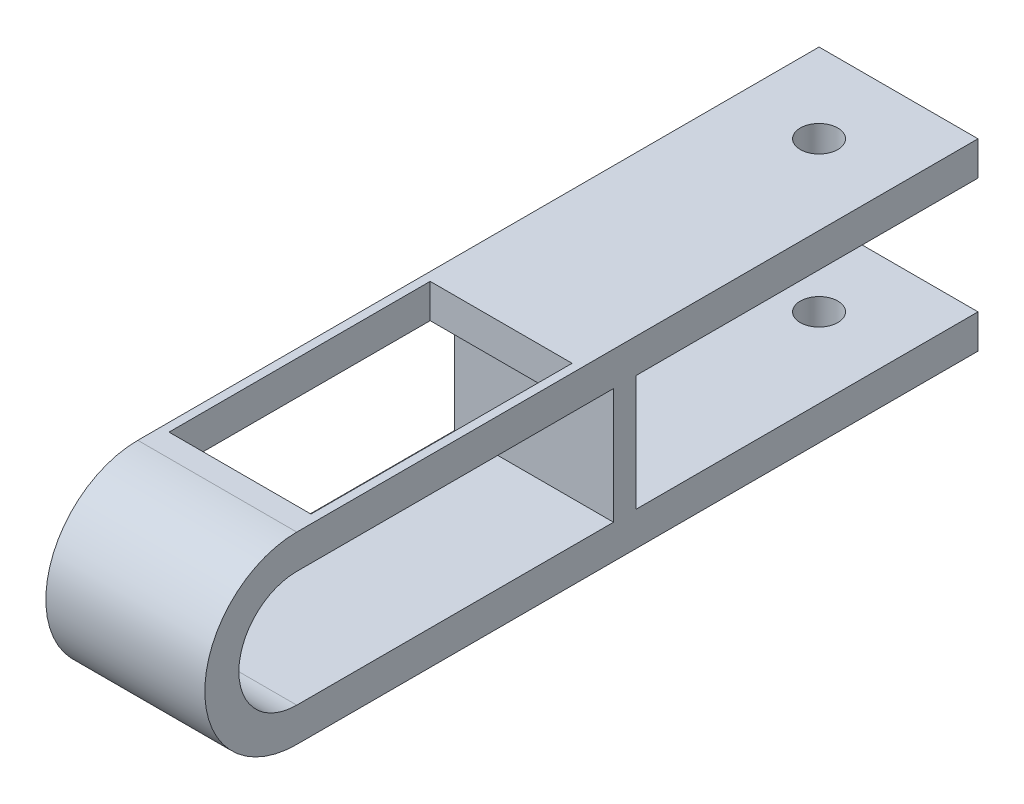
SolidWorks part; units mm, degrees
ref_plane "Front Plane" through (0, 0, 0) normal (1, 0, 0) x (0, 1, 0)
ref_plane "Top Plane" through (0, 0, 0) normal (0, 0, 1) x (0, 1, 0)
ref_plane "Right Plane" through (0, 0, 0) normal (0, 1, 0) x (-1, 0, 0)
sketch "Sketch2" plane through (0, 0, 0) normal (1, 0, 0) x (0, 1, 0)
  line L0 (0, 0) -> (0, 67.6733) construction
  line L1 (8.1, 0) -> (5.1, 0)
  line L3 (-8.1, 60) -> (-8.1, 0)
  line L4 (-8.1, 0) -> (-5.1, 0)
  line L5 (-5.1, 60) -> (-5.1, 32.1)
  line L6 (5.1, 60) -> (5.1, 32.1)
  line L8 (8.1, 60) -> (8.1, 0)
  line L9 (0, 0) -> (-21.6048, 0) construction
  line L10 (-5.1, 30.1) -> (-5.1, 0)
  line L11 (-5.1, 32.1) -> (5.1, 32.1)
  line L13 (-5.1, 30.1) -> (5.1, 30.1)
  line L15 (5.1, 30.1) -> (5.1, 0)
  arc A0 (5.1, 60) -> (-5.1, 60) centre (0, 60) ccw
  arc A1 (8.1, 60) -> (-8.1, 60) centre (0, 60) ccw
  point P16 (0, 65.1)
  point P17 (-5.1, 60)
  dimension "D4" = 2
  dimension "D1" = 3
  dimension "D2" = 60
  dimension "D3" = 5.1
  dimension "D5" = 33
extrude "Boss-Extrude1" add sketch "Sketch2" along normal blind 14
sketch "Sketch3" plane through (0, -8.1, 0) normal (0, -1, 0) x (1, 0, 0)
  line L0 (7, 0) -> (7, 60) construction
  line L1 (14, 0) -> (0, 0) construction
  line L2 (14, 60) -> (0, 60) construction
  line L3 (0, 60) -> (0, 0) construction
  line L4 (14, 60) -> (14, 0) construction
  circle A0 centre (7, 7) radius 1.65
  point P12 (0, 0)
  point P13 (0, 0)
  point P14 (0, 0)
  dimension "D1" = 3.3
  dimension "D2" = 7
extrude "Cut-Extrude1" cut sketch "Sketch3" against normal blind 40
sketch "Sketch4" plane through (0, -8.1, 0) normal (0, -1, 0) x (1, 0, 0)
  line L0 (7, 60) -> (7, 40.4256) construction
  line L1 (14, 60) -> (0, 60) construction
  line L2 (9.35, 38) -> (10.6, 53)
  line L3 (3.4, 53) -> (4.65, 38)
  circle A0 centre (7, 53) radius 3.6
  circle A1 centre (7, 38) radius 2.35
  point P12 (5, 44.8078)
  point P13 (1.4, 58)
  point P14 (0, 0)
  dimension "D1" = 7.2
  dimension "D2" = 4.7
  dimension "D3" = 7
  dimension "D4" = 15
extrude "Cut-Extrude2" cut sketch "Sketch4" against normal blind 1.3 contours A1 L2 A0 L3 | L0 A0 L3 | A0 L0 L2 | A1 region at (8.5274, -8.1, 53.0001) region at (5.4726, -8.1, 53.0001) region at (9.4291, -8.1, 50.1292) region at (7, -8.1, 38)
sketch "Sketch6" plane through (0, -6.8, 0) normal (0, -1, 0) x (1, 0, 0)
  line L0 (7, 35.65) -> (7, 56.6) construction
  circle A0 centre (7, 38) radius 0.15
  arc A1 (4.65, 38) -> (9.35, 38) centre (7, 38) ccw construction
  arc A2 (10.6, 53) -> (3.4, 53) centre (7, 53) ccw construction
  arc A3 (4.65, 38) -> (9.35, 38) centre (7, 38) ccw construction
  point P2 (5, 38.0796)
  dimension "D1" = 0.3
extrude "Cut-Extrude3" cut sketch "Sketch6" against normal blind 0.5
ref_plane "Plane1" through (10.6, -8.1, 53) normal (0, 0, 1) x (1, 0, 0)
sketch "Sketch8" plane through (0, -6.8, 0) normal (0, -1, 0) x (1, 0, 0)
  circle A0 centre (7, 53) radius 0.15
  arc A1 (10.6, 53) -> (3.4, 53) centre (7, 53) ccw construction
  point P5 (5, 53)
  dimension "D1" = 0.3
extrude "Cut-Extrude4" cut sketch "Sketch8" against normal blind 0.5
sketch "Sketch9" plane through (0, 8.1, 0) normal (0, 1, 0) x (-1, 0, 0)
  line L1 (-14, 60) -> (0, 60) construction
  line L2 (-0.75, 35) -> (-13.25, 35)
  line L3 (-0.75, 35) -> (-0.75, 58)
  line L4 (-0.75, 58) -> (-13.25, 58)
  line L5 (-13.25, 35) -> (-13.25, 58)
  line L6 (-0.75, 35) -> (-13.25, 58) construction
  line L7 (-0.75, 58) -> (-13.25, 35) construction
  line L8 (-14, 0) -> (-14, 60) construction
  point P2 (0, 0)
  point P6 (-7, 46.5)
  dimension "D1" = 2
  dimension "D2" = 12.5
  dimension "23" = 23
  dimension "D3" = 0.75
extrude "Cut-Extrude5" cut sketch "Sketch9" against normal up to next
